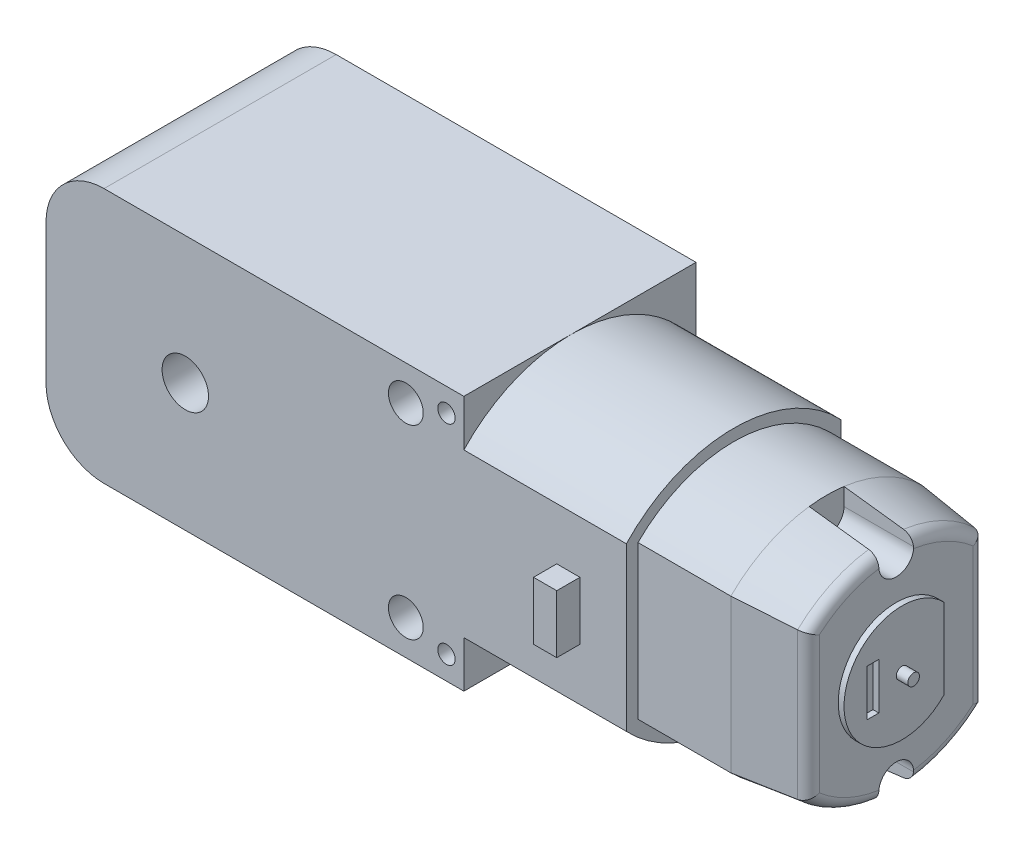
SolidWorks part; units mm, degrees
material "Brass"
ref_plane "Alzado" through (0, 0, 0) normal (0, 0, 1) x (1, 0, 0)
ref_plane "Planta" through (0, 0, 0) normal (0, 1, 0) x (1, 0, 0)
ref_plane "Vista lateral" through (0, 0, 0) normal (1, 0, 0) x (0, 0, -1)
sketch "Croquis1" plane through (0, 0, 0) normal (0, 1, 0) x (1, 0, 0)
  line L1 (-25, -10) -> (25, -10)
  line L2 (-25, -10) -> (-25, 10)
  line L3 (-25, 10) -> (25, 10)
  line L4 (25, -10) -> (25, 10)
  line L5 (-25, -10) -> (25, 10) construction
  line L6 (-25, 10) -> (25, -10) construction
  point P0 (0, 0)
  dimension "D1" = 50
  dimension "D2" = 20
extrude "Saliente-Extruir1" add sketch "Croquis1" along normal mid plane 22
fillet "Redondeo1" radius 5 2 edges at (-25, -11, 0) (-25, 11, 0)
sketch "Croquis2" plane through (25, 0, 0) normal (1, 0, 0) x (0, 0, -1)
  line L0 (-10, 11) -> (-10, -11) construction
  line L2 (-10, 7) -> (-10, -7)
  line L3 (8.5, 7) -> (8.5, -7)
  line L4 (10, 11) -> (10, -11) construction
  line L5 (-10, 11) -> (10, 11) construction
  line L6 (-10, -11) -> (10, -11) construction
  arc A0 (-10, 7) -> (8.5, 7) centre (-0.75, -1.6953) cw
  arc A1 (-10, -7) -> (8.5, -7) centre (-0.75, 1.6953) ccw
  dimension "D1" = 1.5
  dimension "D2" = 4
  dimension "D3" = 4
  dimension "D4" = 4
  dimension "D5" = 4
extrude "Cortar-Extruir1" cut sketch "Croquis2" against normal blind 14 flip side to cut
sketch "Croquis3" plane through (0, 0, -10) normal (0, 0, -1) x (-1, 0, 0)
  line L0 (-11, 11) -> (-11, 7) construction
  line L1 (-11, 11) -> (20, 11) construction
  line L2 (11, 0) -> (-11, 0) construction
  circle A0 centre (-6, 8) radius 1.5
  circle A1 centre (-6, -8) radius 1.5
  dimension "D1" = 3
  dimension "D2" = 5
  dimension "D3" = 3
extrude "Cortar-Extruir2" cut sketch "Croquis3" against normal through all
sketch "Croquis4" plane through (0, 0, 10) normal (0, 0, 1) x (1, 0, 0)
  line L0 (25, 7) -> (25, -7) construction
  line L1 (19, 2.5) -> (21, 2.5)
  line L2 (19, 2.5) -> (19, -2.5)
  line L3 (19, -2.5) -> (21, -2.5)
  line L4 (21, 2.5) -> (21, -2.5)
  point P6 (25, 0)
  point P7 (21, 0)
  dimension "D1" = 4
  dimension "D2" = 2
  dimension "D3" = 5
extrude "Saliente-Extruir2" add sketch "Croquis4" along normal blind 2
sketch "Croquis5" plane through (0, 0, -8.5) normal (0, 0, -1) x (-1, 0, 0)
  line L0 (-19, 2.5) -> (-19, -2.5) construction
  line L2 (-19, 2.5) -> (-21, 2.5) construction
  line L3 (-21, 2.5) -> (-21, -2.5) construction
  line L4 (-25, 7) -> (-25, -7)
  line L5 (-25, -7) -> (-11, -7)
  line L6 (-11, -7) -> (-11, 7)
  line L7 (-11, 7) -> (-25, 7)
  line L8 (-25, 7) -> (-25, -7)
  line L9 (-25, -7) -> (-11, -7)
  line L10 (-11, -7) -> (-11, 7)
  line L11 (-11, 7) -> (-25, 7)
  line L12 (-19, -2.5) -> (-21, -2.5) construction
  line L13 (-19, 2.5) -> (-21, 2.5)
  line L14 (-21, 2.5) -> (-21, -2.5)
  line L15 (-19, -2.5) -> (-21, -2.5)
  line L16 (-19, 2.5) -> (-19, -2.5)
  dimension "D1" = 0
extrude "Saliente-Extruir5" add sketch "Croquis5" along normal blind 2 contours L13 L14 L15 L16
sketch "Croquis6" plane through (0, 0, -10) normal (0, 0, -1) x (-1, 0, 0)
  line L0 (-11, 11) -> (20, 11) construction
  line L1 (-11, 11) -> (-11, 7) construction
  line L2 (-11, -7) -> (-11, -11) construction
  line L3 (-11, -11) -> (20, -11) construction
  line L4 (25, 6) -> (25, -6) construction
  circle A0 centre (-9.5, 9) radius 0.75
  circle A1 centre (-9.5, -9) radius 0.75
  circle A2 centre (4.5, -10) radius 0.25
  circle A3 centre (4.5, 10) radius 0.25
  circle A4 centre (22, 9) radius 0.9
  circle A5 centre (22, -9) radius 0.9
  point P21 (4.5, 11)
  dimension "D2" = 1.5
  dimension "D4" = 1.5
  dimension "D8" = 0.5
  dimension "D10" = 0.5
  dimension "D13" = 1.8
  dimension "D16" = 1.8
  dimension "D1" = 2
  dimension "D3" = 1.5
  dimension "D5" = 1.5
  dimension "D6" = 2
  dimension "D7" = 1
  dimension "D9" = 1
  dimension "D11" = 2
  dimension "D12" = 3
  dimension "D14" = 3
  dimension "D15" = 2
extrude "Cortar-Extruir3" cut sketch "Croquis6" against normal blind 5
sketch "Croquis7" plane through (0, 0, 10) normal (0, 0, 1) x (1, 0, 0)
  circle A0 centre (9.5, -9) radius 0.75 construction
  circle A1 centre (9.5, 9) radius 0.75 construction
  circle A2 centre (9.5, -9) radius 0.75
  circle A3 centre (9.5, 9) radius 0.75
extrude "Cortar-Extruir4" cut sketch "Croquis7" against normal blind 5
sketch "Croquis8" plane through (25, 0, 0) normal (1, 0, 0) x (0, 0, -1)
  line L4 (-9, 6.5943) -> (-9, -6.5943)
  line L5 (7.5, -6.5943) -> (7.5, 6.5943)
  line L6 (-9, 6.5943) -> (-9, -6.5943)
  line L7 (7.5, -6.5943) -> (7.5, 6.5943)
  arc A4 (7.5, 6.5943) -> (-9, 6.5943) centre (-0.75, -1.6953) ccw
  arc A5 (-9, -6.5943) -> (7.5, -6.5943) centre (-0.75, 1.6953) ccw
  arc A6 (7.5, 6.5943) -> (-9, 6.5943) centre (-0.75, -1.6953) ccw
  arc A7 (-9, -6.5943) -> (7.5, -6.5943) centre (-0.75, 1.6953) ccw
  dimension "D1" = 1
extrude "Saliente-Extruir6" add sketch "Croquis8" along normal blind 8
sketch "Croquis9" plane through (0, 0, 10) normal (0, 0, 1) x (1, 0, 0)
  line L0 (-20, 11) -> (11, 11) construction
  line L1 (-25, 6) -> (-25, -6) construction
  circle A0 centre (-13, 0) radius 2
  dimension "D3" = 4
  dimension "D1" = 11
  dimension "D2" = 12
extrude "Cortar-Extruir5" cut sketch "Croquis9" against normal through all
sketch "Croquis11" plane through (33, 0, 0) normal (1, 0, 0) x (0, 0, -1)
  line L2 (-9, 6.5943) -> (-9, -6.5943)
  line L3 (7.5, -6.5943) -> (7.5, 6.5943)
  line L4 (-9, 6.5943) -> (-9, -6.5943)
  line L5 (7.5, -6.5943) -> (7.5, 6.5943)
  arc A2 (7.5, 6.5943) -> (-9, 6.5943) centre (-0.75, -1.6953) ccw
  arc A3 (-9, -6.5943) -> (7.5, -6.5943) centre (-0.75, 1.6953) ccw
  arc A4 (7.5, 6.5943) -> (-9, 6.5943) centre (-0.75, -1.6953) ccw
  arc A5 (-9, -6.5943) -> (7.5, -6.5943) centre (-0.75, 1.6953) ccw
  dimension "D1" = 0
extrude "Saliente-Extruir7" add sketch "Croquis11" along normal blind 6 draft 7
fillet "Redondeo2" radius 1 4 edges at (39, 0, -6.7633) (39, -9.2633, 0.75) (39, 0, 8.2633) (39, 9.2633, 0.75)
sketch "Croquis12" plane through (39, 0, 0) normal (1, 0, 0) x (0, 0, -1)
  line L0 (2.8786, 3.44) -> (2.8786, -3.44)
  line L1 (5.8786, -5.8905) -> (5.8786, 5.8905) construction
  line L3 (-3.75, 2) -> (-2.75, 2)
  line L4 (-3.75, 2) -> (-3.75, -2)
  line L5 (-3.75, -2) -> (-2.75, -2)
  line L6 (-2.75, 2) -> (-2.75, -2)
  arc A0 (2.8786, 3.44) -> (2.8786, -3.44) centre (-0.75, 0) ccw
  arc A1 (5.8786, 5.8905) -> (-7.3786, 5.8905) centre (-0.75, -1.6953) ccw construction
  point P6 (-0.75, 8.3786)
  point P9 (5.8786, 0)
  point P14 (-2.75, 0)
  dimension "D1" = 5
  dimension "D2" = 3
  dimension "D3" = 1
  dimension "D4" = 4
  dimension "D5" = 2
extrude "Saliente-Extruir8" add sketch "Croquis12" along normal blind 0.5
sketch "Croquis13" plane through (39.5, 0, 0) normal (1, 0, 0) x (0, 0, -1)
  circle A0 centre (-0.75, 0) radius 0.5
  dimension "D1" = 1
extrude "Saliente-Extruir9" add sketch "Croquis13" along normal blind 1
sketch "Croquis14" plane through (39, 0, 0) normal (1, 0, 0) x (0, 0, -1)
  line L0 (-2.25, 9.9034) -> (-2.25, 8.4034)
  line L1 (0.75, 8.4034) -> (0.75, 9.9034)
  line L2 (12.375, 0) -> (-12.375, 0) construction
  line L3 (-2.25, -9.9034) -> (-2.25, -8.4034)
  line L4 (0.75, -8.4034) -> (0.75, -9.9034)
  arc A0 (7.5, 6.5943) -> (-9, 6.5943) centre (-0.75, -1.6953) ccw construction
  arc A1 (-2.25, 8.4034) -> (0.75, 8.4034) centre (-0.75, 8.4034) ccw
  arc A2 (0.75, 9.9034) -> (-2.25, 9.9034) centre (-0.75, -1.6953) ccw
  arc A3 (0.75, -9.9034) -> (-2.25, -9.9034) centre (-0.75, 1.6953) cw
  arc A4 (-2.25, -8.4034) -> (0.75, -8.4034) centre (-0.75, -8.4034) cw
  dimension "D1" = 3
  dimension "D2" = 1.5
  dimension "D3" = 1.5
extrude "Cortar-Extruir6" cut sketch "Croquis14" against normal blind 6
sketch "Croquis15" plane through (-25, 0, 0) normal (-1, 0, 0) x (0, 0, 1)
  line L1 (-1, -2.5) -> (1, -2.5)
  line L2 (-1, -2.5) -> (-1, 2.5)
  line L3 (-1, 2.5) -> (1, 2.5)
  line L4 (1, -2.5) -> (1, 2.5)
  line L5 (-1, -2.5) -> (1, 2.5) construction
  line L6 (-1, 2.5) -> (1, -2.5) construction
  point P0 (0, 0)
  dimension "D1" = 2
  dimension "D2" = 5
extrude "Saliente-Extruir10" add sketch "Croquis15" along normal blind 5.5
sketch "Croquis16" plane through (0, 0, 1) normal (0, 0, 1) x (1, 0, 0)
  line L0 (-30.5, 2.5) -> (-25, 2.5) construction
  circle A0 centre (-27.75, 0) radius 1.5
  point P4 (-27.75, 2.5)
  dimension "D1" = 3
extrude "Cortar-Extruir7" cut sketch "Croquis16" against normal through all
